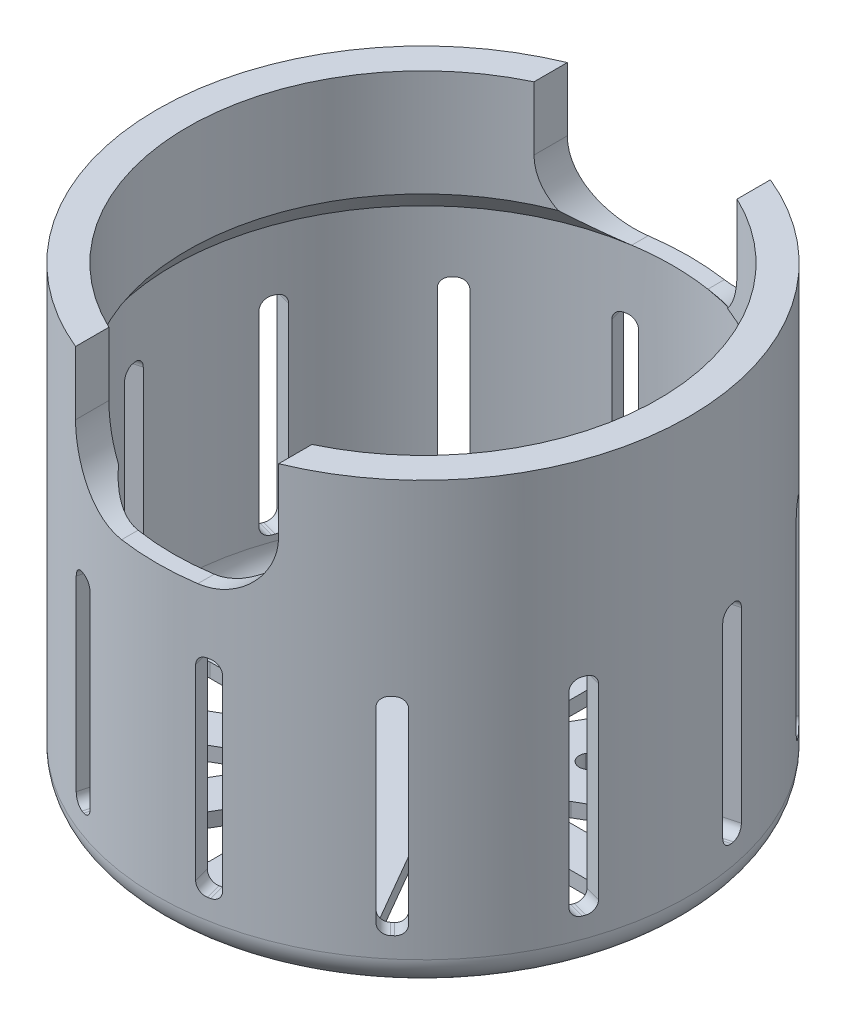
SolidWorks part; units mm, degrees
material "PET"
ref_plane "Front Plane" through (0, 0, 0) normal (0, 0, 1) x (1, 0, 0)
ref_plane "Top Plane" through (0, 0, 0) normal (0, 1, 0) x (1, 0, 0)
ref_plane "Right Plane" through (0, 0, 0) normal (1, 0, 0) x (0, 0, -1)
sketch "Sketch1" plane through (0, 0, 0) normal (0, -1, 0) x (1, 0, 0)
  circle A0 centre (0, 0) radius 11.6 construction
  circle A1 centre (0, 0) radius 11.6
  circle A2 centre (0, 0) radius 13.1
  dimension "D1" = 1.5
extrude "Boss-Extrude1" add sketch "Sketch1" along normal offset from surface (21.25 mm away) 2 offset beyond the face yes
sketch "Sketch2" plane through (0, -21.25, 0) normal (0, -1, 0) x (1, 0, 0)
  circle A0 centre (0, 0) radius 11.6 construction
  circle A1 centre (0, 0) radius 11.6
  circle A2 centre (0, 0) radius 12.3
  dimension "D1" = 0.7
extrude "Cut-Extrude1" cut sketch "Sketch2" against normal up to surface (15 mm away)
sketch "Sketch3" plane through (0, -21.25, 0) normal (0, -1, 0) x (1, 0, 0)
  circle A0 centre (0, 0) radius 13.1 construction
  circle A1 centre (0, 0) radius 13.1
extrude "Boss-Extrude2" add sketch "Sketch3" along normal blind 0.7
fillet "Fillet1" radius 1.5 2 edges at (0, -21.25, -12.3) (0, -21.95, -13.1)
sketch "Sketch4" plane through (0, 0, 0) normal (0, 0, 1) x (1, 0, 0)
  line L0 (-1.875, -3.125) -> (1.875, -3.125) construction
  line L1 (-1.875, 0) -> (1.875, 0)
  line L2 (-1.875, -6.25) -> (1.875, -6.25)
  line L3 (11.6, 0) -> (-11.6, 0) construction
  line L4 (-11.6, -6.25) -> (11.6, -6.25) construction
  line L5 (-11.6, -6.25) -> (11.6, -6.25) construction
  line L6 (0, -3.125) -> (0, 0) construction
  line L7 (5, -3.125) -> (5, 0)
  line L8 (5, 0) -> (1.875, 0)
  line L9 (-5, -3.125) -> (-5, 0)
  line L10 (13.1, 0) -> (-13.1, 0) construction
  line L11 (-5, 0) -> (-1.875, 0)
  arc A0 (-5, -3.125) -> (-1.875, -6.25) centre (-1.875, -3.125) ccw
  arc A1 (1.875, -6.25) -> (5, -3.125) centre (1.875, -3.125) ccw
  point P2 (0, -3.125)
  point P9 (-5, -3.125)
  point P10 (5, -3.125)
  dimension "D1" = 10
extrude "Cut-Extrude2" cut sketch "Sketch4" against normal through all both and the other way through all
sketch "Sketch5" plane through (0, -21.95, 0) normal (0, -1, 0) x (1, 0, 0)
  line L0 (0, 0) -> (0, 13.1) construction
  line L1 (0, 0) -> (-6.55, 11.3449) construction
  line L2 (-4.1592, 9.2039) -> (-1, 3.7321)
  line L3 (-1, 3.7321) -> (-1, 10.0504)
  line L4 (-1, 6.8912) -> (0, 6.8912) construction
  line L5 (-2.5796, 6.468) -> (-3.4456, 5.968) construction
  circle A0 centre (0, 0) radius 13.1 construction
  arc A1 (-4.1592, 9.2039) -> (-1, 10.0504) centre (0, 0) cw
  circle A2 centre (0, 0) radius 11.6 construction
  dimension "D2" = 1.5
  dimension "D1" = 30
  dimension "D3" = 1
extrude "Cut-Extrude3" cut sketch "Sketch5" against normal through all
ref_plane "Plane1" through (-2.5796, 0, 9.6271) normal (0.2588, 0, -0.9659) x (-0.9659, 0, -0.2588)
sketch "Sketch6" plane through (-2.5796, 0, 9.6271) normal (0.2588, 0, -0.9659) x (-0.9659, 0, -0.2588)
  line L0 (-1.6353, -21.25) -> (-1.6353, -21.95) construction
  line L1 (1.6353, -21.25) -> (1.6353, -21.95) construction
  line L2 (-1.6353, -21.25) -> (-1.6353, -21.95) construction
  line L3 (1.6353, -21.25) -> (1.6353, -21.95) construction
  line L4 (13.1, -20.45) -> (-13.1, -20.45) construction
  line L5 (1.6353, -9.25) -> (-1.6353, -9.25)
  line L6 (1.6353, -9.25) -> (1.6353, -19.45)
  line L7 (1.6353, -19.45) -> (-1.6353, -19.45)
  line L8 (-1.6353, -9.25) -> (-1.6353, -19.45)
  line L9 (-1.5445, -6.25) -> (-5.1667, -6.25) construction
  line L10 (0.5, -14.35) -> (1.6353, -14.35) construction
  line L11 (-0.5, -9.25) -> (0.5, -9.25)
  line L12 (-0.5, -9.25) -> (-0.5, -19.45)
  line L13 (-0.5, -19.45) -> (0.5, -19.45)
  line L14 (0.5, -9.25) -> (0.5, -19.45)
  line L15 (-0.5, -14.35) -> (-1.6353, -14.35) construction
  dimension "D1" = 1
  dimension "D2" = 3
  dimension "D3" = 1
extrude "Cut-Extrude4" cut sketch "Sketch6" against normal through all contours L5 L14 L7 L6 region at (-3.6109, -14.35, 9.3508)
fillet "Fillet2" radius 0.5 7 edges at (-4.1592, -21.6, 9.2039) (-1, -21.6, 10.0504) (-1, -21.6, 3.7321) (-4.8392, -19.45, 11.7418) (-4.8392, -9.25, 11.7418) (-3.7674, -19.45, 12.1283) (-3.7674, -9.25, 12.1283)
pattern_circular "CirPattern1" count 12 over 360 about axis through (0, -60.3024, 0) along (0, 1, 0) of "Cut-Extrude3", "Cut-Extrude4", "Fillet2"
chamfer "Chamfer1" distance 1 distance2 0.7 2 edges at (11.6, -6.25, 0) (-11.6, -6.25, 0) first distance on face at (6.9057, -3.3162, -0.0366) first distance on face at (-6.9057, -3.3162, 0.0366)
